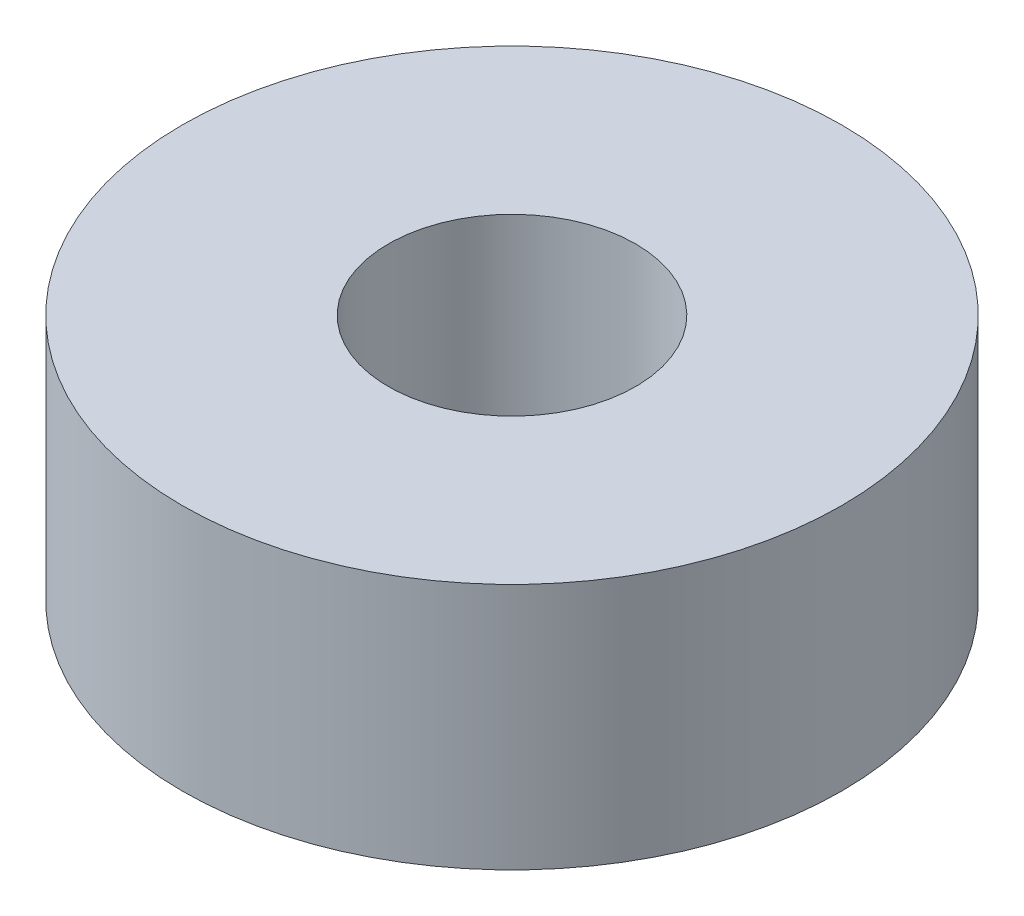
SolidWorks part; units mm, degrees
ref_plane "Front" through (0, 0, 0) normal (0, 0, 1) x (1, 0, 0)
ref_plane "Top" through (0, 0, 0) normal (0, 1, 0) x (1, 0, 0)
ref_plane "Right" through (0, 0, 0) normal (1, 0, 0) x (0, 0, -1)
ref_axis "side-side" through (80.9, 0, 0) along (-1, 0, 0)
ref_axis "up-down" through (0, 50, 0) along (0, -1, 0)
ref_axis "front-back" through (0, 0, -80.9) along (0, 0, 1)
sketch "Sketch1" plane through (0, 0, 0) normal (0, 1, 0) x (1, 0, 0)
  circle A0 centre (0, 0) radius 12.7
  circle A1 centre (0, 0) radius 4.7625
  dimension "D1" = 9.525
  dimension "D2" = 25.4
extrude "Boss-Extrude1" add sketch "Sketch1" along normal mid plane 9.525
